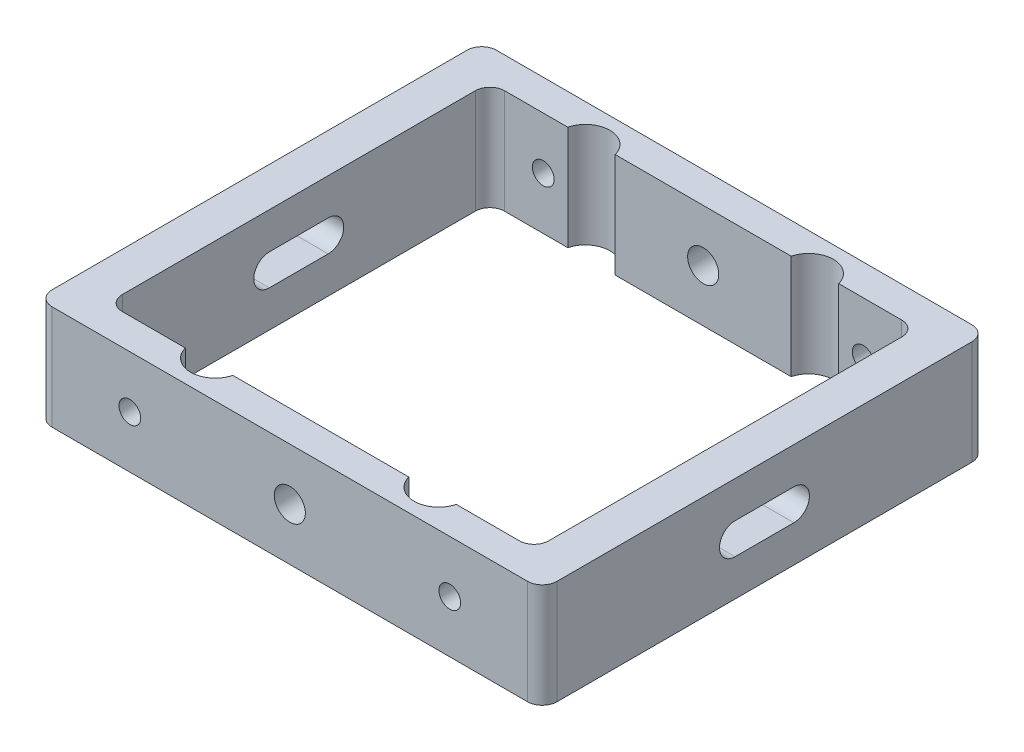
SolidWorks part; units mm, degrees
ref_plane "Front Plane" through (0, 0, 0) normal (0, 0, 1) x (1, 0, 0)
ref_plane "Top Plane" through (0, 0, 0) normal (0, 1, 0) x (1, 0, 0)
ref_plane "Right Plane" through (0, 0, 0) normal (1, 0, 0) x (0, 0, -1)
sketch "Sketch1" plane through (0, 0, 0) normal (0, 1, 0) x (1, 0, 0)
  line L1 (0, 0) -> (60, 0)
  line L2 (0, 0) -> (0, -6.32)
  line L3 (0, -6.32) -> (60, -6.32)
  line L4 (60, 0) -> (60, -6.32)
  dimension "D1" = 60
  dimension "D2" = 6.32
extrude "Boss-Extrude1" add sketch "Sketch1" along normal mid plane 21.28
sketch "Sketch2" plane through (0, 10.64, 0) normal (0, 1, 0) x (1, 0, 0)
  line L0 (0, 0) -> (0, -6.32) construction
  line L1 (0, -6.32) -> (60, -6.32) construction
  line L2 (60, -6.32) -> (60, 0) construction
  circle A0 centre (7.21, 1.25) radius 5
  circle A1 centre (52.79, 1.25) radius 5
  dimension "D1" = 7.21
  dimension "D3" = 7.21
  dimension "D2" = 7.57
  dimension "D4" = 7.57
extrude "Cut-Extrude1" cut sketch "Sketch2" against normal through all
sketch "Sketch3" plane through (60, 0, 0) normal (1, 0, 0) x (0, 0, -1)
  line L1 (-6.32, 10.64) -> (0, 10.64)
  line L2 (-6.32, 10.64) -> (-6.32, -10.64)
  line L3 (-6.32, -10.64) -> (0, -10.64)
  line L4 (0, 10.64) -> (0, -10.64)
extrude "Boss-Extrude2" add sketch "Sketch3" along normal blind 21.5
sketch "Sketch4" plane through (0, 0, 0) normal (-1, 0, 0) x (0, 0, 1)
  line L1 (0, 10.64) -> (6.32, 10.64)
  line L2 (0, 10.64) -> (0, -10.64)
  line L3 (0, -10.64) -> (6.32, -10.64)
  line L4 (6.32, 10.64) -> (6.32, -10.64)
extrude "Boss-Extrude3" add sketch "Sketch4" along normal blind 21.5
sketch "Sketch5" plane through (0, 0, 0) normal (0, 0, -1) x (-1, 0, 0)
  line L5 (-2.3688, -10.64) -> (21.5, -10.64) construction
  line L6 (21.5, 10.64) -> (13.5, 10.64)
  line L7 (21.5, 10.64) -> (21.5, -10.64)
  line L8 (21.5, -10.64) -> (13.5, -10.64)
  line L9 (13.5, 10.64) -> (13.5, -10.64)
  dimension "D1" = 8
extrude "Boss-Extrude6" add sketch "Sketch5" along normal blind 84.33
sketch "Sketch6" plane through (0, 0, 0) normal (0, 0, -1) x (-1, 0, 0)
  line L1 (-81.5, 10.64) -> (-73.5, 10.64)
  line L2 (-81.5, 10.64) -> (-81.5, -10.652)
  line L3 (-81.5, -10.652) -> (-73.5, -10.652)
  line L4 (-73.5, 10.64) -> (-73.5, -10.652)
  dimension "D1" = 8
extrude "Boss-Extrude7" add sketch "Sketch6" along normal blind 84.33
sketch "Sketch7" plane through (73.5, 0, 0) normal (-1, 0, 0) x (0, 0, 1)
  line L0 (-84.33, -10.652) -> (0, -10.652) construction
  line L1 (-84.33, 10.64) -> (-78.01, 10.64)
  line L2 (-84.33, 10.64) -> (-84.33, -10.652)
  line L3 (-84.33, -10.652) -> (-78.01, -10.652)
  line L4 (-78.01, 10.64) -> (-78.01, -10.652)
  dimension "D1" = 6.32
extrude "Boss-Extrude8" add sketch "Sketch7" along normal through all
sketch "Sketch9" plane through (0, 10.64, 0) normal (0, 1, 0) x (1, 0, 0)
  line L0 (-21.5, 84.33) -> (81.5, 84.33) construction
  circle A0 centre (7.21, 76.76) radius 5
  circle A1 centre (52.79, 76.76) radius 5
  dimension "D1" = 7.57
  dimension "D2" = 7.57
  dimension "D3" = 10
extrude "Cut-Extrude2" cut sketch "Sketch9" against normal through all
sketch "Sketch10" plane through (0, 0, -84.33) normal (0, 0, -1) x (-1, 0, 0)
  line L1 (-81.5, -10.64) -> (21.5, -10.64) construction
  line L2 (-30, -10.64) -> (-30, 10.64) construction
  line L3 (21.5, 10.64) -> (-81.5, 10.64) construction
  circle A0 centre (-62.6312, 0.005) radius 2.22
  circle A1 centre (2.6312, 0.005) radius 2.22
  dimension "D1" = 5
  dimension "D2" = 10.645
extrude "Cut-Extrude3" cut sketch "Sketch10" against normal through all
fillet "Fillet1" radius 3 8 edges at (-21.5, 0, 6.32) (81.5, 0, 6.32) (81.5, -0.006, -84.33) (-21.5, -0.006, -84.33) (-13.5, 0, -78.01) (-13.5, 0, 0) (73.5, -0.006, -78.01) (73.5, 0, 0)
sketch "Sketch13" plane through (0, 0, -84.33) normal (0, 0, -1) x (-1, 0, 0)
  line L1 (-78.5, 10.64) -> (-78.5, -10.652) construction
  line L2 (-78.5, -10.64) -> (18.5, -10.64) construction
  circle A0 centre (-30, 0.005) radius 3.175
  dimension "D1" = 48.5
  dimension "D3" = 6.35
  dimension "D2" = 10.645
extrude "Cut-Extrude4" cut sketch "Sketch13" against normal through all
sketch "Sketch16" plane through (0, -10.652, 0) normal (0, -1, 0) x (1, 0, 0)
  line L6 (78.5, -84.33) -> (-18.5, -84.33) construction
  line L7 (25.5729, -84.33) -> (12.6189, -84.33)
  line L8 (25.5729, -84.33) -> (25.5729, -78.01)
  line L9 (25.5729, -78.01) -> (12.6189, -78.01)
  line L10 (12.6189, -84.33) -> (12.6189, -78.01)
  line L11 (12.0512, -78.01) -> (47.9488, -78.01) construction
  dimension "D1" = 12.954
extrude "Cut-Extrude6" [suppressed] cut sketch "Sketch16" against normal mid plane 25.4
sketch "Sketch17" plane through (0, 10.64, 0) normal (0, 1, 0) x (1, 0, 0)
  line L1 (12.6964, 0.5862) -> (25.6504, 0.5862)
  line L2 (12.6964, 0.5862) -> (12.6964, -6.4457)
  line L3 (12.6964, -6.4457) -> (25.6504, -6.4457)
  line L4 (25.6504, 0.5862) -> (25.6504, -6.4457)
  dimension "D1" = 12.954
extrude "Cut-Extrude7" [suppressed] cut sketch "Sketch17" against normal mid plane 25.4
sketch "Sketch18" [suppressed] plane through (0, 0, 6.32) normal (0, 0, 1) x (1, 0, 0)
  line L0 (12.6964, -2.06) -> (25.6504, -2.06) construction
  line L1 (19.1734, -2.06) -> (25.6504, -2.06)
  line L2 (19.1734, -2.06) -> (19.1734, -10.64)
  line L3 (19.1734, -10.64) -> (25.6504, -10.64)
  line L4 (25.6504, -2.06) -> (25.6504, -10.64)
  line L5 (-18.5, -10.64) -> (78.5, -10.64) construction
extrude "Cut-Extrude8" [suppressed] cut sketch "Sketch18" against normal up to next
sketch "Sketch19" plane through (-21.5, 0, 0) normal (-1, 0, 0) x (0, 0, 1)
  line L0 (-81.33, 10.64) -> (-81.33, -10.652) construction
  line L1 (-45.005, 3.175) -> (-33.005, 3.175)
  line L2 (-45.005, -3.175) -> (-33.005, -3.175)
  arc A1 (-45.005, 3.175) -> (-45.005, -3.175) centre (-45.005, 0) ccw
  arc A2 (-33.005, -3.175) -> (-33.005, 3.175) centre (-33.005, 0) ccw
  dimension "D1" = 36.325
  dimension "D2" = 12
extrude "Cut-Extrude9" cut sketch "Sketch19" against normal through all
